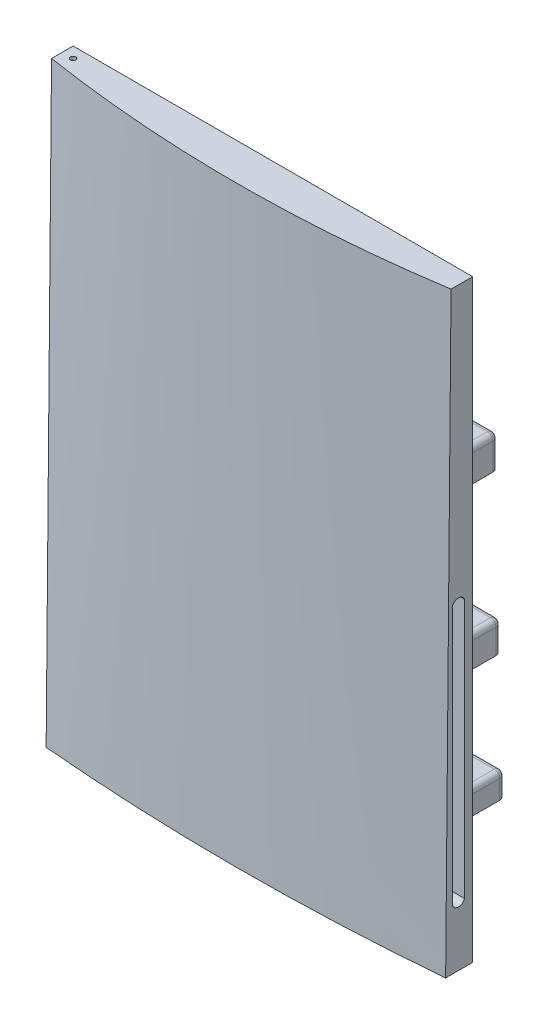
SolidWorks part; units mm, degrees
material "Aço cromo inoxidável"
ref_plane "Plano frontal" through (0, 0, 0) normal (0, 0, 1) x (1, 0, 0)
ref_plane "Plano superior" through (0, 0, 0) normal (0, 1, 0) x (1, 0, 0)
ref_plane "Plano direito" through (0, 0, 0) normal (1, 0, 0) x (0, 0, -1)
sketch "Esboço1" plane through (0, 0, 0) normal (0, 1, 0) x (1, 0, 0)
  line L0 (-370, 0) -> (370, 0)
  line L1 (-370, 0) -> (-370, -50)
  line L2 (370, 0) -> (370, -50)
  arc A0 (-370, -50) -> (370, -50) centre (0, 4133.6706) ccw
  point P3 (0, 0)
  dimension "D1" = 740
  dimension "D3" = 4200
  dimension "D2" = 50
ref_plane "Plano1" through (0, 1100, 0) normal (0, 1, 0) x (1, 0, 0)
sketch "Esboço2" plane through (0, 1100, 0) normal (0, 1, 0) x (1, 0, 0)
  line L0 (370, 0) -> (370, -50) construction
  line L1 (-370, 0) -> (370, 0)
  line L2 (-370, 0) -> (-370, -40)
  line L4 (370, 0) -> (370, -40)
  arc A0 (-370, -40) -> (370, -40) centre (0, 2331.3077) ccw
  dimension "D2" = 2400
  dimension "D1" = 40
  dimension "D3" = 740
loft "Loft1" add profiles "Esboço2", "Esboço1"
sketch "Esboço5" plane through (0, 0, 0) normal (0, -1, 0) x (1, 0, 0)
  line L0 (-370, 0) -> (-370, 50) construction
  line L1 (370, 0) -> (-370, 0) construction
  circle A0 centre (-350, 20) radius 5
  dimension "D3" = 10
  dimension "D1" = 20
  dimension "D2" = 20
extrude "Corte-extrusão3" cut sketch "Esboço5" against normal up to next contours A0
sketch "Esboço6" plane through (0, 0, 0) normal (0, -1, 0) x (1, 0, 0)
  line L1 (-370, 0) -> (-320.8568, 0)
  line L2 (-370, 0) -> (-370, 25.4419)
  line L3 (-370, 25.4419) -> (-335.8568, 25.4419)
  line L4 (-320.8568, 0) -> (-320.8568, 10.4419)
  arc A0 (-335.8568, 25.4419) -> (-320.8568, 10.4419) centre (-335.8568, 10.4419) cw
  dimension "D1" = 15
extrude "Corte-extrusão4" cut sketch "Esboço6" against normal blind 10 contours L3 A0 L4 L1 L2
sketch "Esboço8" plane through (0, 0, 0) normal (0, 0, -1) x (-1, 0, 0)
  line L1 (335, 35) -> (-345, 35)
  line L2 (335, 35) -> (335, 1075)
  line L3 (335, 1075) -> (-345, 1075)
  line L4 (-345, 35) -> (-345, 1075)
  line L5 (-370, 1100) -> (-370, 0) construction
  line L6 (370, 1100) -> (370, 10) construction
  line L7 (114.7854, 1100) -> (-114.7854, 1100) construction
  line L8 (370, 10) -> (320.8568, 10) construction
  dimension "D1" = 25
  dimension "D2" = 25
  dimension "D3" = 35
  dimension "D4" = 25
extrude "Ressalto-extrusão1" add sketch "Esboço8" along normal blind 20
fillet "Filete1" radius 10 9 edges at (5, 1075, 0) (345, 1075, -10) (345, 555, -20) (345, 555, 0) (-335, 555, -20) (-335, 1075, -10) (-335, 555, 0) (5, 35, -20) (5, 35, 0)
sketch "Esboço11" plane through (370, 0, 0) normal (1, 0, 0) x (0, 0, -1)
  line L1 (0, 1100) -> (0, 0) construction
  line L2 (-37.5, 110) -> (-15, 110)
  line L3 (-37.5, 110) -> (-37.5, 590)
  line L4 (-37.5, 590) -> (-15, 590)
  line L5 (-15, 110) -> (-15, 590)
  line L6 (-50, 0) -> (0, 0) construction
  dimension "D1" = 480
  dimension "D2" = 15
  dimension "D3" = 110
  dimension "D4" = 22.5
extrude "Corte-extrusão5" cut sketch "Esboço11" against normal blind 35
sketch "Esboço12" plane through (370, 0, 0) normal (1, 0, 0) x (0, 0, -1)
  line L0 (-15, 110) -> (-37.5, 110)
  line L1 (-15, 590) -> (-37.5, 590)
  arc A0 (-15, 110) -> (-37.5, 110) centre (-26.25, 114.1758) cw
  arc A1 (-15, 590) -> (-37.5, 590) centre (-26.25, 585.8242) ccw
  dimension "D1" = 12
  dimension "D2" = 12
extrude "Corte-extrusão6" cut sketch "Esboço12" against normal blind 35
fillet "Filete15" radius 10 1 edges at (335, 350, 37.5)
sketch "Esboço13" plane through (0, 0, -20) normal (0, 0, -1) x (-1, 0, 0)
  line L0 (260, 155) -> (250, 155)
  line L2 (260, 155) -> (260, 200)
  line L3 (260, 200) -> (-290, 200)
  line L4 (-290, 155) -> (-290, 200)
  line L5 (250, 155) -> (250, 190)
  line L6 (250, 190) -> (-280, 190)
  line L7 (-280, 190) -> (-280, 155)
  line L8 (-280, 155) -> (-290, 155)
  line L9 (325, 45) -> (325, 1075) construction
  line L10 (-335, 1075) -> (-335, 45) construction
  line L12 (-335, 45) -> (325, 45) construction
  dimension "D1" = 10
  dimension "D2" = 65
  dimension "D3" = 45
  dimension "D4" = 155
  dimension "D5" = 10
  dimension "D6" = 110
extrude "Ressalto-extrusão2" add sketch "Esboço13" along normal blind 120 contours L6 L7 L8 L4 L3 L2 L0 L5
sketch "Esboço14" plane through (0, 190, 0) normal (0, -1, 0) x (1, 0, 0)
  line L0 (-250, -140) -> (-250, -20) construction
  line L1 (-250, -130) -> (279.5185, -130)
  line L2 (-250, -130) -> (-250, -140)
  line L3 (-250, -140) -> (279.5185, -140)
  line L4 (279.5185, -130) -> (279.5185, -140)
  dimension "D1" = 10
fillet "Filete16" radius 10 5 edges at (290, 200, -80) (-260, 200, -80) (15, 200, -140) (-260, 177.5, -140) (290, 177.5, -140)
sketch "Esboço15" plane through (0, 0, -20) normal (0, 0, -1) x (-1, 0, 0)
  line L0 (260.2613, 247) -> (-263.4354, 247) construction
  line L1 (-370, 0) -> (320.8568, 0) construction
  line L2 (260.2613, 474) -> (-263.4354, 474) construction
  line L3 (253.7766, 383.4194) -> (243.7766, 383.4194)
  line L5 (253.7766, 383.4194) -> (253.7766, 429.5574)
  line L6 (253.7766, 429.5574) -> (-86.1612, 429.5574)
  line L7 (-86.1612, 383.4194) -> (-86.1612, 429.5574)
  line L8 (243.7766, 383.4194) -> (243.7766, 419.5574)
  line L9 (243.7766, 419.5574) -> (-76.1612, 419.5574)
  line L10 (-76.1612, 419.5574) -> (-76.1612, 383.4194)
  line L11 (-76.1612, 383.4194) -> (-86.1612, 383.4194)
  line L12 (370, 1100) -> (370, 10) construction
  dimension "D1" = 247
  dimension "D2" = 474
  dimension "D3" = 10
  dimension "D4" = 10
  dimension "D5" = 419.5574
  dimension "D6" = 456.1612
  dimension "D7" = 46.138
  dimension "D8" = 116.2234
extrude "Ressalto-extrusão4" add sketch "Esboço15" along normal blind 120
sketch "Esboço16" plane through (0, 419.5574, 0) normal (0, -1, 0) x (1, 0, 0)
  line L0 (-243.7766, -140) -> (-243.7766, -20) construction
  line L1 (-243.7766, -130) -> (76.1612, -130)
  line L2 (-243.7766, -130) -> (-243.7766, -140)
  line L3 (-243.7766, -140) -> (76.1612, -140)
  line L4 (76.1612, -130) -> (76.1612, -140)
  dimension "D1" = 10
extrude "Ressalto-extrusão5" add sketch "Esboço16" along normal blind 36.138
fillet "Filete17" radius 10 5 edges at (86.1612, 406.4884, -140) (86.1612, 429.5574, -80) (-253.7766, 429.5574, -80) (-83.8077, 429.5574, -140) (-253.7766, 406.4884, -140)
sketch "Esboço17" plane through (0, 0, -20) normal (0, 0, -1) x (-1, 0, 0)
  line L2 (-100.263, 439.5574) -> (-283, 439.5574)
  line L3 (-100.263, 439.5574) -> (-100.263, 383.4194)
  line L5 (-283, 439.5574) -> (-283, 383.4194)
  line L7 (-100.263, 383.4194) -> (-110.263, 383.4194)
  line L8 (-110.263, 383.4194) -> (-110.263, 429.5574)
  line L9 (-110.263, 429.5574) -> (-273, 429.5574)
  line L10 (-273, 429.5574) -> (-273, 383.4194)
  line L11 (-273, 383.4194) -> (-283, 383.4194)
  line L12 (-335, 1075) -> (-335, 45) construction
  line L16 (-370, 1100) -> (-370, 0) construction
  line L17 (-335, 45) -> (325, 45) construction
  dimension "D1" = 10
  dimension "D2" = 10
  dimension "D3" = 234.737
  dimension "D4" = 87
  dimension "D5" = 394.5574
extrude "Ressalto-extrusão6" add sketch "Esboço17" along normal blind 120
sketch "Esboço18" plane through (0, 429.5574, 0) normal (0, -1, 0) x (-1, 0, 0)
  line L0 (-110.263, 140) -> (-110.263, 20) construction
  line L1 (-110.263, 130) -> (-273, 130)
  line L2 (-110.263, 130) -> (-110.263, 140)
  line L3 (-110.263, 140) -> (-273, 140)
  line L4 (-273, 130) -> (-273, 140)
  dimension "D1" = 10
extrude "Ressalto-extrusão7" add sketch "Esboço18" along normal blind 46.138
fillet "Filete18" radius 10 5 edges at (100.263, 439.5574, -80) (191.6315, 439.5574, -140) (283, 439.5574, -80) (100.263, 411.4884, -140) (283, 411.4884, -140)
sketch "Esboço19" plane through (0, 0, -20) normal (0, 0, -1) x (-1, 0, 0)
  line L0 (228.1383, 679.5574) -> (-142.0108, 679.5574) construction
  line L2 (243.7766, 419.5574) -> (-76.1612, 419.5574) construction
  line L3 (253.7766, 735) -> (253.7766, 725)
  line L6 (253.7766, 735) -> (-277.3494, 735)
  line L8 (253.7766, 725) -> (-277.3494, 725)
  line L9 (-277.3494, 725) -> (-277.3494, 735)
  line L10 (370, 1100) -> (370, 0) construction
  line L11 (325, 1075) -> (-335, 1075) construction
  line L12 (-370, 1100) -> (-370, 0) construction
  dimension "D1" = 260
  dimension "D2" = 10
  dimension "D3" = 116.2234
  dimension "D4" = 350
  dimension "D5" = 92.6506
extrude "Ressalto-extrusão8" add sketch "Esboço19" along normal blind 120
sketch "Esboço20" plane through (0, 725, 0) normal (0, -1, 0) x (1, 0, 0)
  line L0 (-253.7766, -20) -> (-253.7766, -140)
  line L1 (-253.7766, -140) -> (277.3494, -140)
  line L2 (277.3494, -140) -> (277.3494, -20)
  line L3 (277.3494, -20) -> (267.3494, -20)
  line L4 (277.3494, -20) -> (-253.7766, -20) construction
  line L5 (267.3494, -20) -> (267.3494, -130)
  line L6 (267.3494, -130) -> (-243.7766, -130)
  line L7 (-243.7766, -130) -> (-243.7766, -20)
  line L8 (-243.7766, -20) -> (-253.7766, -20)
  dimension "D1" = 10
  dimension "D2" = 10
extrude "Ressalto-extrusão9" add sketch "Esboço20" along normal blind 50
fillet "Filete19" radius 10 5 edges at (-253.7766, 735, -80) (277.3494, 735, -80) (11.7864, 735, -140) (277.3494, 705, -140) (-253.7766, 705, -140)
sketch "Esboço22" plane through (0, 190, 0) normal (0, -1, 0) x (1, 0, 0)
  line L0 (-250, -140) -> (-250, -130)
  line L1 (-250, -130) -> (279.5185, -130)
  line L2 (279.5185, -130) -> (279.5185, -140)
  line L3 (279.5185, -140) -> (-250, -140)
extrude "Ressalto-extrusão10" add sketch "Esboço22" along normal blind 35
